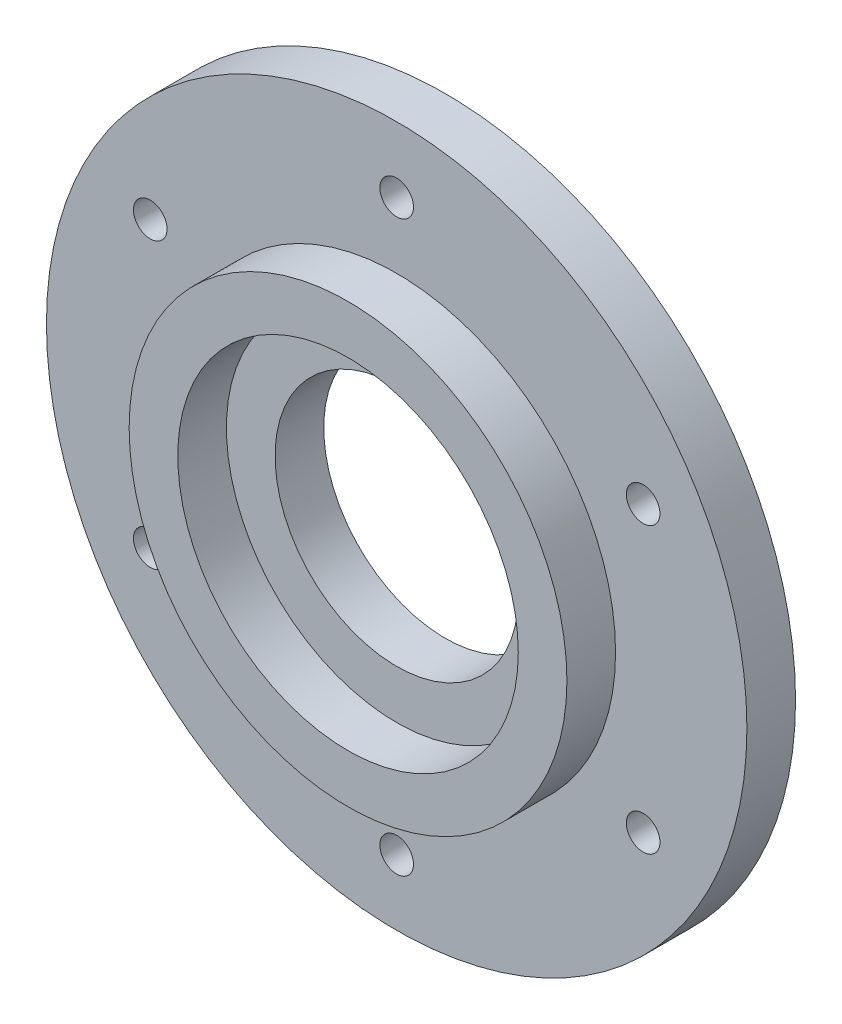
SolidWorks part; units mm, degrees
material "6061-T6 (SS)"
ref_plane "Front Plane" through (0, 0, 0) normal (0, 0, 1) x (1, 0, 0)
ref_plane "Top Plane" through (0, 0, 0) normal (0, 1, 0) x (1, 0, 0)
ref_plane "Right Plane" through (0, 0, 0) normal (1, 0, 0) x (0, 0, -1)
sketch "Sketch Spindle Skeleton" plane through (0, 0, 0) normal (1, 0, 0) x (0, 0, -1)
  line L0 (-119.9, -9.5) -> (-144, -9.5)
  line L5 (-1000, 0) -> (49000, 0)
  line L6 (0, -9.5) -> (0, 9.5)
  line L13 (0, 9.5) -> (-48.3, 9.5)
  line L26 (-48.3, 9.5) -> (-48.3, 14)
  line L27 (-48.3, 14) -> (-119.9, 14)
  line L32 (-119.9, 14) -> (-119.9, 9.5)
  line L34 (-160, 7) -> (-160, -7)
  line L36 (-119.9, -9.5) -> (-119.9, -14)
  line L37 (-119.9, -14) -> (-48.3, -14)
  line L38 (-48.3, -14) -> (-48.3, -9.5)
  line L39 (0, -9.5) -> (-48.3, -9.5)
  line L40 (-24.2, 36) -> (-19.2, 36)
  line L41 (-136.5, 22.5) -> (-119.9, 22.5)
  line L42 (-136.5, 22.5) -> (-136.5, -22.5)
  line L43 (-136.5, -22.5) -> (-119.9, -22.5)
  line L44 (-119.9, 22.5) -> (-119.9, -22.5)
  line L45 (-136.5, 22.5) -> (-119.9, -22.5) construction
  line L46 (-136.5, -22.5) -> (-119.9, 22.5) construction
  line L47 (-31.7, 22.5) -> (-48.3, 22.5)
  line L48 (-31.7, 22.5) -> (-31.7, -22.5)
  line L49 (-31.7, -22.5) -> (-48.3, -22.5)
  line L50 (-48.3, 22.5) -> (-48.3, -22.5)
  line L51 (-31.7, 22.5) -> (-48.3, -22.5) construction
  line L52 (-31.7, -22.5) -> (-48.3, 22.5) construction
  line L59 (-19.2, 36) -> (-19.2, -36)
  line L60 (-19.2, -36) -> (-24.2, -36)
  line L61 (-24.2, -22.5) -> (-29.2, -22.5)
  line L62 (-29.2, -22.5) -> (-29.2, -17.5)
  line L63 (-29.2, -17.5) -> (-24.2, -17.5)
  line L64 (-24.2, -17.5) -> (-24.2, 17.5)
  line L65 (-24.2, 17.5) -> (-29.2, 17.5)
  line L66 (-29.2, 17.5) -> (-29.2, 22.5)
  line L67 (-29.2, 22.5) -> (-24.2, 22.5)
  line L68 (-24.2, 22.5) -> (-24.2, 36)
  line L69 (-24.2, -22.5) -> (-24.2, -36)
  line L71 (-141.5, 36) -> (-25.2, 36)
  line L72 (-141.5, 36) -> (-141.5, -36)
  line L73 (-141.5, -36) -> (-25.2, -36)
  line L74 (-25.2, 36) -> (-25.2, -36)
  line L75 (-141.5, 36) -> (-25.2, -36) construction
  line L76 (-141.5, -36) -> (-25.2, 36) construction
  line L77 (-144, -9.5) -> (-144, -7)
  line L78 (-144, -7) -> (-160, -7)
  line L79 (-119.9, 9.5) -> (-144, 9.5)
  line L80 (-144, 7) -> (-160, 7)
  line L81 (-144, 9.5) -> (-144, 7)
  line L82 (-131.95, 9.5) -> (-131.95, -9.5) construction
  line L83 (-24.15, 9.5) -> (-24.15, -9.5) construction
  point P3 (0, 0)
  point P18 (-128.2, 0)
  point P24 (-40, 0)
  point P29 (-83.35, 0)
  point P48 (-19.2, 29.25)
revolve "Main Revolve" add sketch "Sketch Spindle Skeleton" angle 360 about L5 region at (0, 22.65, 21.8091) region at (0, 20, 27.2)
sketch "Sketch Center Cut" plane through (0, 0, 24.2) normal (0, 0, 1) x (1, 0, 0)
  circle A0 centre (0, 0) radius 17.5 construction
  circle A1 centre (0, 0) radius 17.5 construction
  circle A2 centre (0, 0) radius 12.5
  dimension "D1" = 5
extrude "Cut Center" cut sketch "Sketch Center Cut" against normal through all
hole_wizard "CBORE for #5 Binding Head Machine Screw1" positions "Hole wizard sketch 1" profile "Hole wizard sketch 2" counterbore size "#5" standard "ANSI Inch" end condition through all
sketch "Hole wizard sketch 1" plane through (0, 0, 19.2) normal (0, 0, -1) x (-1, 0, 0)
  point P0 (0, 29.25)
sketch "Hole wizard sketch 2" plane through (0, 29.25, 19.2) normal (1, 0, 0) x (0, 1, 0)
  line L0 (0, 0) -> (0, 10)
  line L1 (0, 10) -> (1.7272, 10)
  line L3 (1.7272, 10) -> (1.7272, 1.9812)
  line L4 (1.7272, 1.9812) -> (3.7706, 1.9812)
  line L5 (3.7706, 1.9812) -> (3.7706, 0)
  line L7 (3.7706, 0) -> (0, 0)
  line L11 (0, -6.35) -> (0, 107.95) construction
  dimension "Thru Hole Dia." = 3.4544
  dimension "Thru Hole Depth" = 10
  dimension "C'Bore Dia." = 7.5413
  dimension "C'Bore Depth" = 1.9812
pattern_circular "CirPattern1" count 6 over 360 about axis through (0, 0, 19.2) along (0, 0, 1) of "CBORE for #5 Binding Head Machine Screw1"
